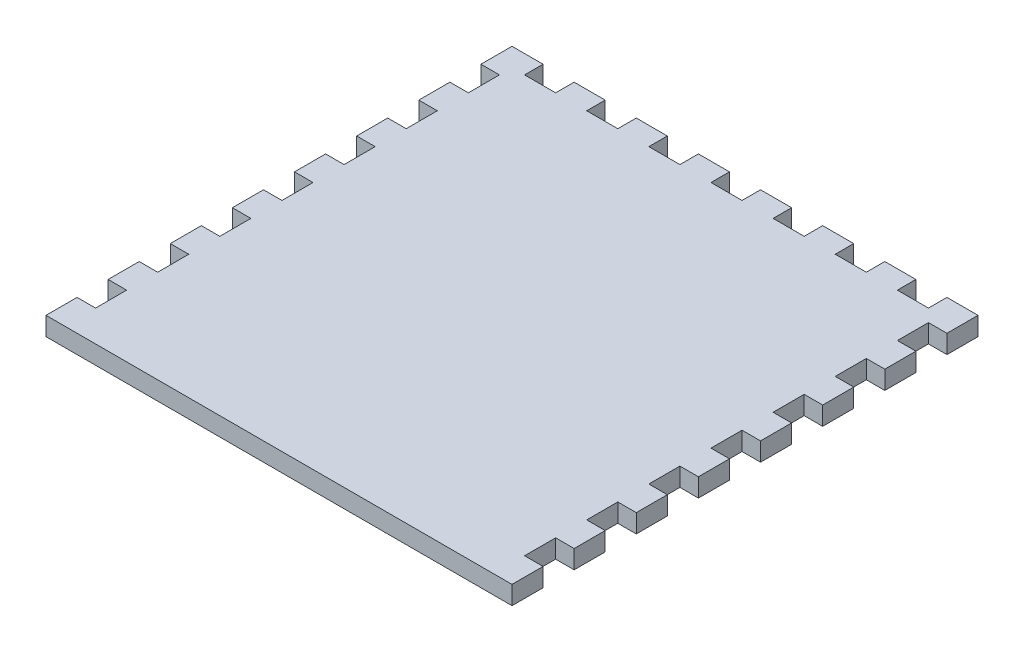
SolidWorks part; units mm, degrees
material "Acrylic (Medium-high impact)"
ref_plane "Front Plane" through (0, 0, 0) normal (0, 0, 1) x (1, 0, 0)
ref_plane "Top Plane" through (0, 0, 0) normal (0, 1, 0) x (1, 0, 0)
ref_plane "Right Plane" through (0, 0, 0) normal (1, 0, 0) x (0, 0, -1)
sketch "Sketch1" plane through (0, 0, 0) normal (0, 1, 0) x (1, 0, 0)
  line L1 (-40, -40) -> (40, -40)
  line L2 (-40, -40) -> (-40, 40)
  line L3 (-40, 40) -> (40, 40)
  line L4 (40, -40) -> (40, 40)
  line L5 (-40, -40) -> (40, 40) construction
  line L6 (-40, 40) -> (40, -40) construction
  point P0 (0, 0)
  dimension "D1" = 80
  dimension "D2" = 80
extrude "Boss-Extrude1" add sketch "Sketch1" along normal blind 3.175
sketch "Sketch2" plane through (0, 3.175, 0) normal (0, 1, 0) x (1, 0, 0)
  line L0 (0, 0) -> (50000, 0) construction
  line L1 (40, -40) -> (40, 40) construction
  line L2 (-34.6667, -40) -> (-34.6667, -36.825)
  line L3 (-40, -40) -> (40, -40) construction
  line L4 (-34.6667, -36.825) -> (-29.3333, -36.825)
  line L5 (-29.3333, -36.825) -> (-29.3333, -40)
  line L6 (-40, 24) -> (-40, 29.3333)
  line L7 (-40, 18.6667) -> (-40, 13.3333)
  line L8 (-24, -40) -> (-24, -36.825)
  line L9 (-24, -36.825) -> (-18.6667, -36.825)
  line L10 (-18.6667, -36.825) -> (-18.6667, -40)
  line L11 (-40, 8) -> (-40, 2.6667)
  line L12 (-13.3333, -40) -> (-13.3333, -36.825)
  line L13 (-13.3333, -36.825) -> (-8, -36.825)
  line L14 (-8, -36.825) -> (-8, -40)
  line L15 (-40, -2.6667) -> (-40, -8)
  line L16 (-2.6667, -40) -> (-2.6667, -36.825)
  line L17 (-2.6667, -36.825) -> (2.6667, -36.825)
  line L18 (2.6667, -36.825) -> (2.6667, -40)
  line L19 (-40, -13.3333) -> (-40, -18.6667)
  line L20 (8, -40) -> (8, -36.825)
  line L21 (8, -36.825) -> (13.3333, -36.825)
  line L22 (13.3333, -36.825) -> (13.3333, -40)
  line L23 (-40, -24) -> (-40, -29.3333)
  line L24 (18.6667, -40) -> (18.6667, -36.825)
  line L25 (18.6667, -36.825) -> (24, -36.825)
  line L26 (24, -36.825) -> (24, -40)
  line L28 (29.3333, -40) -> (29.3333, -36.825)
  line L29 (29.3333, -36.825) -> (34.6667, -36.825)
  line L30 (34.6667, -36.825) -> (34.6667, -40)
  line L33 (34.6667, 36.825) -> (34.6667, 40)
  line L34 (29.3333, 36.825) -> (34.6667, 36.825)
  line L35 (29.3333, 40) -> (29.3333, 36.825)
  line L37 (24, 36.825) -> (24, 40)
  line L38 (18.6667, 36.825) -> (24, 36.825)
  line L39 (18.6667, 40) -> (18.6667, 36.825)
  line L41 (13.3333, 36.825) -> (13.3333, 40)
  line L42 (8, 36.825) -> (13.3333, 36.825)
  line L43 (8, 40) -> (8, 36.825)
  line L45 (2.6667, 36.825) -> (2.6667, 40)
  line L46 (-2.6667, 36.825) -> (2.6667, 36.825)
  line L47 (-2.6667, 40) -> (-2.6667, 36.825)
  line L49 (-8, 36.825) -> (-8, 40)
  line L50 (-13.3333, 36.825) -> (-8, 36.825)
  line L51 (-13.3333, 40) -> (-13.3333, 36.825)
  line L53 (-18.6667, 36.825) -> (-18.6667, 40)
  line L54 (-24, 36.825) -> (-18.6667, 36.825)
  line L55 (-24, 40) -> (-24, 36.825)
  line L58 (-29.3333, 36.825) -> (-29.3333, 40)
  line L59 (-34.6667, 36.825) -> (-29.3333, 36.825)
  line L60 (-34.6667, 40) -> (-34.6667, 36.825)
  line L61 (40, 40) -> (40, 34.6667)
  line L62 (40, 34.6667) -> (36.825, 34.6667)
  line L63 (36.825, 34.6667) -> (36.825, 29.3333)
  line L64 (36.825, 29.3333) -> (40, 29.3333)
  line L66 (40, 34.6667) -> (40, 24)
  line L67 (40, 24) -> (36.825, 24)
  line L69 (36.825, 24) -> (36.825, 18.6667)
  line L70 (36.825, 18.6667) -> (40, 18.6667)
  line L71 (40, 24) -> (40, 13.3333)
  line L72 (40, 13.3333) -> (36.825, 13.3333)
  line L74 (36.825, 13.3333) -> (36.825, 8)
  line L75 (36.825, 8) -> (40, 8)
  line L76 (40, 13.3333) -> (40, 2.6667)
  line L77 (40, 2.6667) -> (36.825, 2.6667)
  line L79 (36.825, 2.6667) -> (36.825, -2.6667)
  line L80 (36.825, -2.6667) -> (40, -2.6667)
  line L81 (40, 2.6667) -> (40, -8)
  line L82 (40, -8) -> (36.825, -8)
  line L84 (36.825, -8) -> (36.825, -13.3333)
  line L85 (36.825, -13.3333) -> (40, -13.3333)
  line L86 (40, -8) -> (40, -18.6667)
  line L87 (40, -18.6667) -> (36.825, -18.6667)
  line L89 (36.825, -18.6667) -> (36.825, -24)
  line L90 (36.825, -24) -> (40, -24)
  line L91 (40, -18.6667) -> (40, -29.3333)
  line L92 (40, -29.3333) -> (36.825, -29.3333)
  line L93 (40, -29.3333) -> (40, -34.6667)
  line L94 (36.825, -29.3333) -> (36.825, -34.6667)
  line L95 (36.825, -34.6667) -> (40, -34.6667)
  line L96 (40, -34.6667) -> (40, -40)
  line L97 (0, 0) -> (0, 50000) construction
  line L98 (40, 40) -> (-40, 40) construction
  line L99 (0, 0) -> (-50000, 0) construction
  line L100 (-40, -34.6667) -> (-40, -40)
  line L101 (-36.825, -34.6667) -> (-40, -34.6667)
  line L102 (-36.825, -29.3333) -> (-36.825, -34.6667)
  line L103 (-40, -29.3333) -> (-40, -34.6667)
  line L104 (-40, -29.3333) -> (-36.825, -29.3333)
  line L105 (-40, -18.6667) -> (-40, -29.3333)
  line L106 (-36.825, -24) -> (-40, -24)
  line L107 (-36.825, -18.6667) -> (-36.825, -24)
  line L109 (-40, -18.6667) -> (-36.825, -18.6667)
  line L110 (-40, -8) -> (-40, -18.6667)
  line L111 (-36.825, -13.3333) -> (-40, -13.3333)
  line L112 (-36.825, -8) -> (-36.825, -13.3333)
  line L114 (-40, -8) -> (-36.825, -8)
  line L115 (-40, 2.6667) -> (-40, -8)
  line L116 (-36.825, -2.6667) -> (-40, -2.6667)
  line L117 (-36.825, 2.6667) -> (-36.825, -2.6667)
  line L119 (-40, 2.6667) -> (-36.825, 2.6667)
  line L120 (-40, 13.3333) -> (-40, 2.6667)
  line L121 (-36.825, 8) -> (-40, 8)
  line L122 (-36.825, 13.3333) -> (-36.825, 8)
  line L124 (-40, 13.3333) -> (-36.825, 13.3333)
  line L125 (-40, 24) -> (-40, 13.3333)
  line L126 (-36.825, 18.6667) -> (-40, 18.6667)
  line L127 (-36.825, 24) -> (-36.825, 18.6667)
  line L129 (-40, 24) -> (-36.825, 24)
  line L130 (-40, 34.6667) -> (-40, 24)
  line L131 (-36.825, 29.3333) -> (-40, 29.3333)
  line L133 (-36.825, 34.6667) -> (-36.825, 29.3333)
  line L134 (-40, 34.6667) -> (-36.825, 34.6667)
  line L135 (-40, 40) -> (-40, 34.6667)
  line L136 (40, 29.3333) -> (40, 24) [skipped]
  line L137 (40, 18.6667) -> (40, 13.3333) [skipped]
  line L138 (40, 8) -> (40, 2.6667) [skipped]
  line L139 (40, -2.6667) -> (40, -8) [skipped]
  line L140 (40, -13.3333) -> (40, -18.6667) [skipped]
  line L141 (40, -24) -> (40, -29.3333) [skipped]
  line L142 (-40, 40) -> (40, 40)
  line L143 (-40, -40) -> (40, -40)
  point P5 (40, 0)
  point P110 (0, 40)
  line M33 (-40, 40) -> (-40, -40)
  line M34 (-40, -40) -> (40, -40)
  dimension "D1" = 3.175
  dimension "D4" = 7
  dimension "D6" = 7
extrude "Cut-Extrude3" cut sketch "Sketch2" against normal through all flip side to cut contours L134 L133 L131 L130 L129 L127 L126 L125 L124 L122 L121 L120 L119 L117 L116 L115 L114 L112 L111 L110 L109 L107 L106 L105 L104 L102 L101 L2 L4 L5 L8 L9 L10 L12 L13 L14 L16 L17 L18 L20 L21 L22 L24 M33 M34 region at (0, 3.175, 0)
sketch "Sketch3" plane through (0, 0, 0) normal (0, -1, 0) x (1, 0, 0)
  line L1 (-40, 40) -> (40, 40)
  line L2 (-40, 40) -> (-40, 34.6667)
  line L3 (-40, 34.6667) -> (40, 34.6667)
  line L4 (40, 40) -> (40, 34.6667)
extrude "Boss-Extrude2" add sketch "Sketch3" against normal up to surface (3.175 mm away) up to face at (0, 3.175, 0)
